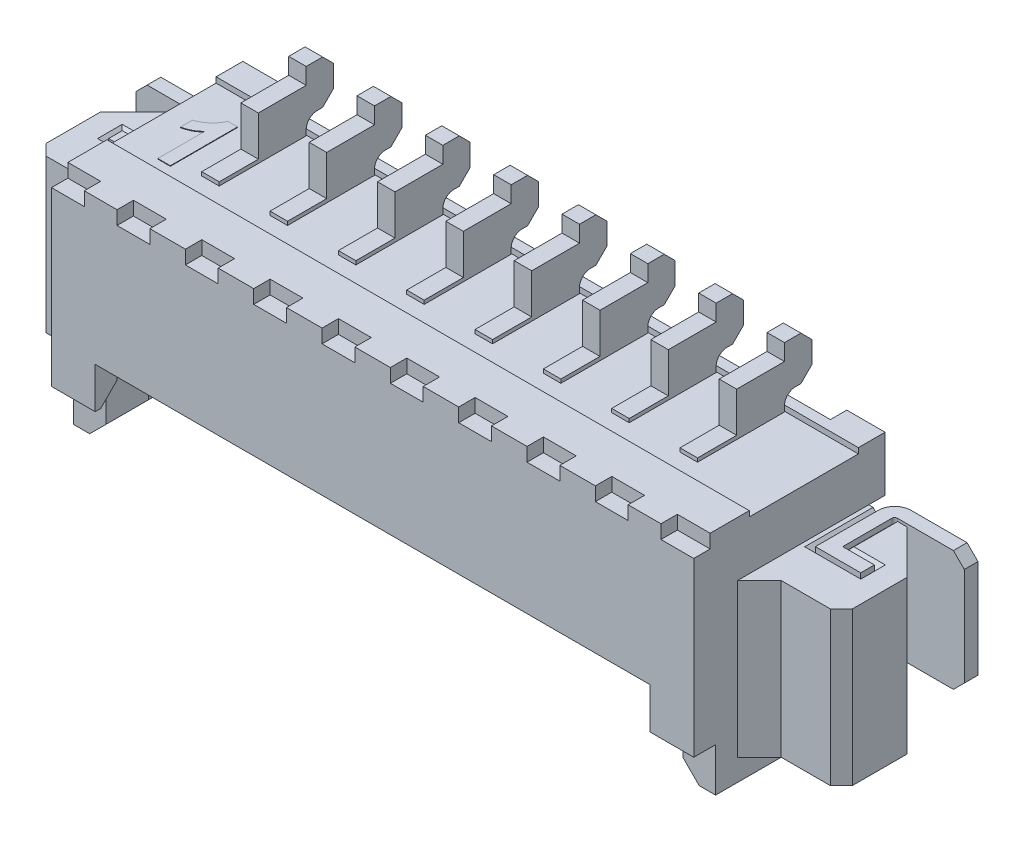
SolidWorks part; units mm, degrees
ref_plane "Спереди" through (0, 0, 0) normal (0, 0, 1) x (1, 0, 0)
ref_plane "Сверху" through (0, 0, 0) normal (0, 1, 0) x (1, 0, 0)
ref_plane "Справа" through (0, 0, 0) normal (1, 0, 0) x (0, 0, -1)
sketch "Эскиз1" plane through (0, 0, 0) normal (0, 1, 0) x (1, 0, 0)
  line L0 (5.275, -1.5) -> (5.275, -0.7)
  line L1 (-5.875, -0.3) -> (-5.875, -3.1)
  line L2 (5.575, -1.5) -> (5.275, -1.5)
  line L3 (-5.575, -2.325) -> (-5.575, -1.5)
  line L4 (-5.875, -3.1) -> (-5.275, -3.1)
  line L5 (-5.575, -2.325) -> (-5.275, -2.325)
  line L6 (-5.275, -2.325) -> (-5.275, -3.1)
  line L7 (5.275, -2.325) -> (5.275, -3.1)
  line L8 (5.575, -2.325) -> (5.275, -2.325)
  line L9 (0, -1.9) -> (0, -3.3692) construction
  line L10 (-5.575, -1.5) -> (-5.275, -1.5)
  line L11 (-5.275, -1.5) -> (-5.275, -0.7)
  line L12 (5.875, -3.1) -> (5.275, -3.1)
  line L13 (5.575, -2.325) -> (5.575, -1.5)
  line L14 (5.875, -0.3) -> (5.875, -3.1)
  line L15 (-5.875, -0.3) -> (5.875, -0.3)
  line L16 (5.275, -0.7) -> (-5.275, -0.7)
  dimension "D1" = 0.6
  dimension "D2" = 0.3
  dimension "D3" = 0.3
  dimension "D4" = 2.8
  dimension "D5" = 5.875
extrude "Вытянуть1" add sketch "Эскиз1" against normal blind 4.2
sketch "Эскиз2" plane through (0, 0, 0) normal (0, 1, 0) x (1, 0, 0)
  line L0 (-5.875, -3.1) -> (-5.275, -3.1)
  line L1 (-5.275, -3.1) -> (-5.275, -3.5)
  line L2 (-5.875, -3.1) -> (-5.875, -3.5)
  line L3 (-5.875, -3.5) -> (-5.275, -3.5)
  line L4 (0, -2.1744) -> (0, -2.7597) construction
  line L5 (5.875, -3.5) -> (5.275, -3.5)
  line L6 (5.875, -3.1) -> (5.875, -3.5)
  line L7 (5.275, -3.1) -> (5.275, -3.5)
  line L8 (5.875, -3.1) -> (5.275, -3.1)
extrude "Вытянуть2" add sketch "Эскиз2" against normal blind 3.4
sketch "Эскиз3" plane through (0, 0, 0) normal (0, 1, 0) x (1, 0, 0)
  line L0 (0, -2.5358) -> (0, -3.4442) construction
  line L1 (-5.275, -3.1) -> (-5.075, -3.1)
  line L2 (-5.275, -3.5) -> (-5.275, -2.325) construction
  line L3 (-5.075, -3.1) -> (-5.075, -3.5)
  line L4 (-5.075, -3.5) -> (-5.275, -3.5)
  line L5 (-5.275, -3.5) -> (-5.275, -3.1)
  line L6 (5.275, -3.5) -> (5.275, -3.1)
  line L7 (5.075, -3.5) -> (5.275, -3.5)
  line L8 (5.075, -3.1) -> (5.075, -3.5)
  line L9 (5.275, -3.1) -> (5.075, -3.1)
  dimension "D1" = 0.2
extrude "Вытянуть3" add sketch "Эскиз3" against normal blind 3.4
sketch "Эскиз5" plane through (0, 0, 0) normal (0, 1, 0) x (1, 0, 0)
  line L0 (-5.075, -3.1) -> (-5.075, -3.5)
  line L1 (5.075, -3.1) -> (5.075, -3.5)
  line L2 (5.075, -3.5) -> (-5.075, -3.5)
  line L3 (-5.075, -3.1) -> (5.075, -3.1)
extrude "Вытянуть4" add sketch "Эскиз5" against normal blind 2.65
chamfer "Фаска1" distance 0.3 angle 45 8 edges at (0, -2.65, 3.1) (5.175, -3.4, 3.1) (-5.175, -3.4, 3.1) (5.275, -4.2, 2.7125) (5.275, -4.2, 1.1) (0, -4.2, 0.7) (-5.275, -4.2, 1.1) (-5.275, -4.2, 2.7125)
sketch "Эскиз6" plane through (0, 0, 0) normal (0, 0, 1) x (1, 0, 0)
  line L0 (0, -1.2805) -> (0, -2.2251) construction
  line L1 (-4.375, -1.55) -> (-3.125, -1.55)
  line L2 (-3.125, -1.55) -> (-3.125, -2.7)
  line L3 (-4.375, -2.7) -> (-3.91, -2.7)
  line L4 (-4.375, -2.7) -> (-4.375, -1.55)
  line L5 (-5.875, -3.4) -> (-5.875, 0) construction
  line L6 (3.59, -4.5729) -> (3.59, -2.7)
  line L7 (3.91, -4.5729) -> (3.59, -4.5729)
  line L8 (3.91, -2.7) -> (3.91, -4.5729)
  line L9 (3.125, -2.7) -> (3.59, -2.7)
  line L10 (-3.125, -2.7) -> (-3.59, -2.7)
  line L11 (-3.91, -2.7) -> (-3.91, -4.5729)
  line L12 (-3.91, -4.5729) -> (-3.59, -4.5729)
  line L13 (-3.59, -4.5729) -> (-3.59, -2.7)
  line L14 (4.375, -2.7) -> (4.375, -1.55)
  line L15 (4.375, -2.7) -> (3.91, -2.7)
  line L16 (3.125, -1.55) -> (3.125, -2.7)
  line L17 (4.375, -1.55) -> (3.125, -1.55)
  dimension "D1" = 1.25
  dimension "D2" = 1.5
  dimension "D3" = 0.465
  dimension "D4" = 0.465
extrude "Вытянуть5" cut sketch "Эскиз6" along normal blind 0.6 from offset 0.2
sketch "Эскиз7" [suppressed] plane through (0, 0, 0) normal (0, 0, 1) x (1, 0, 0)
  line L0 (-0.16, -2.7) -> (-0.625, -2.7)
  line L1 (0.625, -2.7) -> (0.625, -1.55)
  line L2 (0.625, -1.55) -> (-0.625, -1.55)
  line L3 (-0.625, -1.55) -> (-0.625, -2.7)
  line L4 (-0.16, -2.7) -> (-0.16, -4.3)
  line L5 (0.16, -2.7) -> (0.16, -4.3)
  line L6 (0.16, -2.7) -> (0.625, -2.7)
  line L7 (0.16, -4.3) -> (-0.16, -4.3)
extrude "Вытянуть6" [suppressed] cut sketch "Эскиз7" along normal blind 0.6 from offset 0.2
sketch "Эскиз8" plane through (0, 0, 0) normal (0, 1, 0) x (1, 0, 0)
  line L0 (-5.875, -3.5) -> (-5.875, -0.3)
  line L1 (-5.875, -0.3) -> (-5.875, -3.5) construction
  line L2 (5.875, -3.5) -> (5.875, -0.3)
  line L3 (5.875, -3.5) -> (5.875, -0.3) construction
  line L4 (-5.875, -0.3) -> (5.875, -0.3)
  line L5 (5.875, -3.5) -> (-5.875, -3.5)
extrude "Вытянуть7" add sketch "Эскиз8" against normal blind 1.3
sketch "Эскиз9" plane through (0, 0, 0) normal (0, 0, 1) x (1, 0, 0)
  line L0 (0, -1.6402) -> (0, 1.5884) construction
  line L1 (-5.875, 0) -> (-5.175, 0)
  line L2 (-5.875, 0) -> (5.875, 0) construction
  line L3 (-5.175, 0) -> (-5.175, -1)
  line L4 (-5.875, 0) -> (-5.875, -1)
  line L5 (-5.875, -3.4) -> (-5.875, 0) construction
  line L6 (-5.875, -1) -> (-5.175, -1)
  line L7 (5.875, -1) -> (5.175, -1)
  line L8 (5.875, 0) -> (5.875, -1)
  line L9 (5.175, 0) -> (5.175, -1)
  line L10 (5.875, 0) -> (5.175, 0)
  line L11 (-5.175, -2.9) -> (-5.175, -4.2)
  line L12 (5.575, -4.2) -> (3.91, -4.2) construction
  line L13 (-5.175, -4.2) -> (-5.875, -4.2)
  line L14 (-5.875, -4.2) -> (-5.875, -2.9)
  line L15 (-5.875, -2.9) -> (-5.175, -2.9)
  line L16 (5.875, -2.9) -> (5.175, -2.9)
  line L17 (5.875, -4.2) -> (5.875, -2.9)
  line L18 (5.175, -4.2) -> (5.875, -4.2)
  line L19 (5.175, -2.9) -> (5.175, -4.2)
  dimension "D1" = 0.7
extrude "Вытянуть8" add sketch "Эскиз9" along normal blind 0.3
sketch "Эскиз11" plane through (0, 0, 0) normal (0, 1, 0) x (1, 0, 0)
  line L0 (0.465, -1.075) -> (0.785, -1.075)
  line L1 (0.785, -1.075) -> (0.785, -1.775)
  line L2 (0.785, -1.775) -> (0.465, -1.775)
  line L3 (0.465, -1.775) -> (0.465, -1.075)
  line L4 (0, -0.51) -> (0, -0.8079) construction
  dimension "D1" = 0.32
  dimension "D2" = 0.785
extrude "Вытянуть10" add sketch "Эскиз11" along normal blind 3 and the other way blind 0.25 draft 25 from offset 3.3 offset against normal yes
sketch "Эскиз16" plane through (0, 0, 0) normal (0, 1, 0) x (1, 0, 0)
  line L0 (0, -2.2797) -> (0, -3.0653) construction
  line L1 (0.325, -3.2) -> (0.925, -3.2)
  line L2 (0.925, -3.2) -> (0.925, -3.5)
  line L3 (0.925, -3.5) -> (0.325, -3.5)
  line L4 (0.325, -3.5) -> (0.325, -3.2)
  dimension "D1" = 0.6
  dimension "D2" = 0.925
extrude "Вытянуть15" cut sketch "Эскиз16" against normal blind 0.25
sketch "Эскиз17" plane through (0, 0, 0) normal (0, 1, 0) x (1, 0, 0)
  line L0 (0, -1.6063) -> (0, -2.1824)
  line L1 (5.275, -3.2) -> (5.875, -3.2)
  line L2 (5.875, -3.2) -> (5.875, -3.5)
  line L3 (5.875, -3.5) -> (5.275, -3.5)
  line L4 (5.275, -3.5) -> (5.275, -3.2)
  line L5 (5.875, -3.5) -> (5.875, 0) construction
  line L6 (-5.275, -3.5) -> (-5.275, -3.2)
  line L7 (-5.875, -3.5) -> (-5.275, -3.5)
  line L8 (-5.875, -3.2) -> (-5.875, -3.5)
  line L9 (-5.275, -3.2) -> (-5.875, -3.2)
  dimension "D1" = 0.6
  dimension "D2" = 0.6
extrude "Вытянуть16" cut sketch "Эскиз17" against normal blind 0.25 contours L4 L3 L2 L1 | L6 L9 L8 L7 region at (5.575, 0, 3.35) region at (-5.575, 0, 3.35)
sketch "Эскиз19" plane through (0, 0, 0) normal (0, 1, 0) x (1, 0, 0)
  line L0 (-4.975, -2.2255) -> (-4.975, -0.9961)
  line L1 (-4.975, -0.9961) -> (-5.1496, -0.9961)
  line L2 (-4.975, -2.2255) -> (-5.204, -2.2255)
  line L3 (-5.204, -2.2255) -> (-5.204, -1.3668)
  line L4 (-5.4947, -1.3027) -> (-5.4947, -1.5216)
  line L5 (-5.875, 0) -> (-5.875, -3.2) construction
  arc A0 (-5.4947, -1.3027) -> (-5.1496, -0.9961) centre (-5.6805, -0.7461) ccw
  arc A1 (-5.204, -1.3668) -> (-5.4947, -1.5216) centre (-5.5969, -0.9794) cw
  dimension "D1" = 0.229
  dimension "D2" = 0.8587
  dimension "D3" = 0.2907
  dimension "D4" = 1.2293
  dimension "D5" = 0.1746
  dimension "D6" = 0.4473
  dimension "D7" = 0.4765
  dimension "D8" = 0.2189
  dimension "D9" = 0.9
sketch "Эскиз22" plane through (0.785, 0, 0) normal (1, 0, 0) x (0, 0, -1)
  line L0 (-1.375, 0.7) -> (-1.375, -0.0318)
  line L1 (-0.5, 1) -> (-0.5, 0.7)
  line L2 (-0.5, 1) -> (-0.2, 1)
  line L3 (0, 0.8) -> (0, 0.4)
  line L4 (-0.2, 0.2) -> (-0.3, 0.2)
  line L5 (-0.5, 0.7) -> (-1.375, 0.7)
  line L6 (-1.375, -0.2) -> (-0.5, -0.2)
  line L7 (-0.5, -0.2) -> (-0.5, 0)
  line L8 (-0.2, 1) -> (0, 0.8)
  line L9 (0, 0.4) -> (-0.2, 0.2)
  line L10 (-1.375, -0.0318) -> (-2.091, -0.0318)
  line L11 (-2.091, -0.0318) -> (-2.091, -0.2)
  line L12 (-2.091, -0.2) -> (-1.375, -0.2)
  arc A0 (-0.3, 0.2) -> (-0.5, 0) centre (-0.3, 0) ccw
  point P5 (0, 1)
  point P6 (0, 0.2)
  dimension "D1" = 0.2
sketch "Эскиз24" plane through (0, 0, 0) normal (0, 1, 0) x (1, 0, 0)
  line L0 (0, -1.766) -> (0, -2.4846) construction
  line L1 (-5.875, -0.4884) -> (-5.875, -2.4846)
  line L2 (-5.875, 0) -> (-5.875, -3.2) construction
  line L3 (5.875, -0.4884) -> (5.875, -2.4846)
  line L4 (-5.875, -0.4884) -> (5.875, -0.4884)
  line L5 (5.875, -2.4846) -> (-5.875, -2.4846)
extrude "Вытянуть28" cut sketch "Эскиз24" against normal blind 0.1
extrude "Вытянуть29" add sketch "Эскиз19" along normal blind 0.01 from offset 0.1 offset against normal yes
extrude "Вытянуть30" add sketch "Эскиз22" against normal blind 0.32
pattern_linear "Линейный массив1" count 4 spacing 1.25 along (1, 0, 0) count 5 spacing 1.25 along (-1, 0, 0) of "Вытянуть15"
pattern_linear "Линейный массив17" count 5 spacing 1.25 along (-1, 0, 0) count 4 spacing 1.25 along (1, 0, 0) of "Вытянуть10", "Вытянуть30"
sketch "Эскиз26" plane through (0, 0, 0) normal (0, 1, 0) x (1, 0, 0)
  line L0 (-7.375, -1.1) -> (-7.375, -2.1)
  line L1 (-5.875, -0.4884) -> (-5.875, -2.4846) construction
  line L2 (-5.875, -0.3) -> (-6.575, -0.3)
  line L3 (-5.875, -0.3) -> (-5.875, -2.7)
  line L4 (0, -0.0818) -> (0, -1.0086) construction
  line L5 (-5.875, 0) -> (-5.875, -3.1) construction
  line L6 (-7.175, -2.3) -> (-6.275, -2.3)
  line L7 (-6.275, -2.3) -> (-5.875, -2.7)
  line L8 (-6.575, -0.3) -> (-7.375, -1.1)
  line L9 (-7.375, -2.1) -> (-7.175, -2.3)
  line L10 (7.375, -2.1) -> (7.175, -2.3)
  line L11 (6.575, -0.3) -> (7.375, -1.1)
  line L12 (6.275, -2.3) -> (5.875, -2.7)
  line L13 (7.175, -2.3) -> (6.275, -2.3)
  line L14 (5.875, -0.3) -> (5.875, -2.7)
  line L15 (5.875, -0.3) -> (6.575, -0.3)
  line L16 (7.375, -1.1) -> (7.375, -2.1)
  point P13 (-7.375, -0.3)
  point P15 (-7.375, -2.3)
  point P24 (7.375, -2.3)
  point P25 (7.375, -0.3)
  dimension "D1" = 1.5
  dimension "D2" = 0.4
extrude "Вытянуть31" add sketch "Эскиз26" against normal blind 2.8 from offset 1 offset against normal yes
sketch "Эскиз27" plane through (0, 0, 0) normal (0, 1, 0) x (1, 0, 0)
  line L0 (-6.055, -0.2231) -> (-6.055, -1.45)
  line L1 (-6.055, -1.45) -> (-6.8808, -1.45)
  line L2 (-6.8808, -1.45) -> (-6.8808, -1.2)
  line L3 (-6.8808, -1.2) -> (-6.305, -1.2)
  line L4 (-6.305, -1.2) -> (-6.305, -0.2231)
  line L5 (-6.305, -0.2231) -> (-6.055, -0.2231)
  line L6 (0, 0.061) -> (0, -0.7665) construction
  line L7 (-5.875, -2.7) -> (-5.875, -0.3) construction
  line L8 (6.305, -0.2231) -> (6.055, -0.2231)
  line L9 (6.305, -1.2) -> (6.305, -0.2231)
  line L10 (6.8808, -1.2) -> (6.305, -1.2)
  line L11 (6.8808, -1.45) -> (6.8808, -1.2)
  line L12 (6.055, -1.45) -> (6.8808, -1.45)
  line L13 (6.055, -0.2231) -> (6.055, -1.45)
  dimension "D1" = 0.18
  dimension "D2" = 0.25
  dimension "D3" = 0.8258
extrude "Вытянуть32" cut sketch "Эскиз27" along normal blind 0.11 draft 45 from offset 1.1 draft outward yes offset against normal yes
sketch "Эскиз28" plane through (0, 0, 0) normal (0, 1, 0) x (1, 0, 0)
  line L0 (-7.575, 0) -> (-6.35, 0)
  line L1 (-6.05, -0.3) -> (-6.05, -1.45)
  line L2 (-6.05, -1.45) -> (-6.88, -1.45)
  line L3 (-6.88, -1.45) -> (-6.88, -1.2)
  line L4 (-6.88, -1.2) -> (-6.3, -1.2)
  line L5 (-6.3, -1.2) -> (-6.3, -0.3)
  line L6 (-6.35, -0.25) -> (-7.575, -0.25)
  line L7 (-7.575, -0.25) -> (-7.575, 0)
  line L8 (-5.875, -0.4884) -> (-5.875, -2.4846) construction
  line L9 (0, 0.2762) -> (0, -0.1789) construction
  line L10 (7.575, -0.25) -> (7.575, 0)
  line L11 (6.35, -0.25) -> (7.575, -0.25)
  line L12 (6.3, -1.2) -> (6.3, -0.3)
  line L13 (6.88, -1.2) -> (6.3, -1.2)
  line L14 (6.88, -1.45) -> (6.88, -1.2)
  line L15 (6.05, -1.45) -> (6.88, -1.45)
  line L16 (6.05, -0.3) -> (6.05, -1.45)
  line L17 (7.575, 0) -> (6.35, 0)
  arc A0 (-6.35, 0) -> (-6.05, -0.3) centre (-6.35, -0.3) cw
  arc A1 (-6.3, -0.3) -> (-6.35, -0.25) centre (-6.35, -0.3) ccw
  arc A2 (6.3, -0.3) -> (6.35, -0.25) centre (6.35, -0.3) cw
  arc A3 (6.35, 0) -> (6.05, -0.3) centre (6.35, -0.3) ccw
  dimension "D1" = 0.3
  dimension "D2" = 0.05
  dimension "D3" = 0.175
  dimension "D4" = 0.25
  dimension "D5" = 1.275
  dimension "D6" = 0.58
extrude "Вытянуть33" add sketch "Эскиз28" against normal blind 2.2 from offset 1 offset against normal yes
chamfer "Фаска2" distance 0.2 angle 45 4 edges at (7.575, -1, 0.125) (7.575, -3.2, 0.125) (-7.575, -1, 0.125) (-7.575, -3.2, 0.125)
